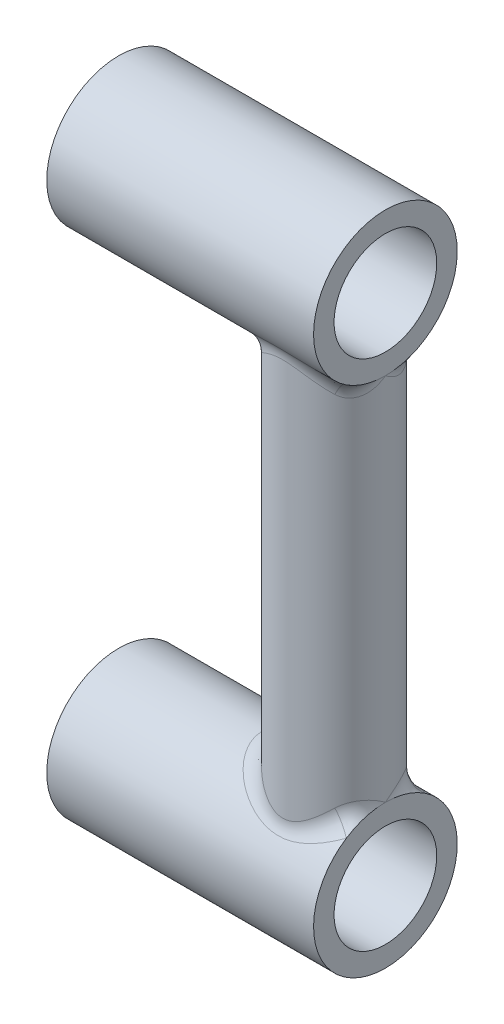
SolidWorks part; units mm, degrees
material "ABS"
ref_plane "Front Plane" through (0, 0, 0) normal (0, 0, 1) x (1, 0, 0)
ref_plane "Top Plane" through (0, 0, 0) normal (0, 1, 0) x (1, 0, 0)
ref_plane "Right Plane" through (0, 0, 0) normal (1, 0, 0) x (0, 0, -1)
sketch "Sketch1" plane through (0, 0, 0) normal (1, 0, 0) x (0, 0, -1)
  circle A0 centre (0, 0) radius 8.89
  dimension "D1" = 17.78
extrude "Boss-Extrude1" add sketch "Sketch1" along normal blind 33.02
sketch "Sketch2" plane through (0, 0, 0) normal (0, 1, 0) x (1, 0, 0)
  circle A1 centre (26.67, 0) radius 6.35
extrude "Boss-Extrude2" add sketch "Sketch2" along normal blind 63.5
sketch "Sketch3" plane through (33.02, 0, 0) normal (1, 0, 0) x (0, 0, -1)
  circle A0 centre (0, 0) radius 6.35
  dimension "D1" = 12.7
extrude "Cut-Extrude2" cut sketch "Sketch3" against normal through all both and the other way through all
sketch "Sketch4" plane through (0, 0, 0) normal (1, 0, 0) x (0, 0, -1)
  line L0 (6.35, 63.5) -> (-6.35, 63.5) construction
  circle A0 centre (0, 63.5) radius 8.89
  dimension "D1" = 17.78
extrude "Boss-Extrude3" add sketch "Sketch4" along normal blind 33.02
sketch "Sketch5" plane through (33.02, 0, 0) normal (1, 0, 0) x (0, 0, -1)
  circle A0 centre (0, 63.5) radius 6.35
  dimension "D1" = 12.7
extrude "Cut-Extrude3" cut sketch "Sketch5" against normal through all both
scale "Scale1" scale about centroid uniform scaling yes scale factor 3
fillet "Fillet1" radius 7.62 1 edges at (19.3236, 100.3502, -1.037)
fillet "Fillet2" radius 7.62 1 edges at (19.3236, -36.8502, -1.037)
